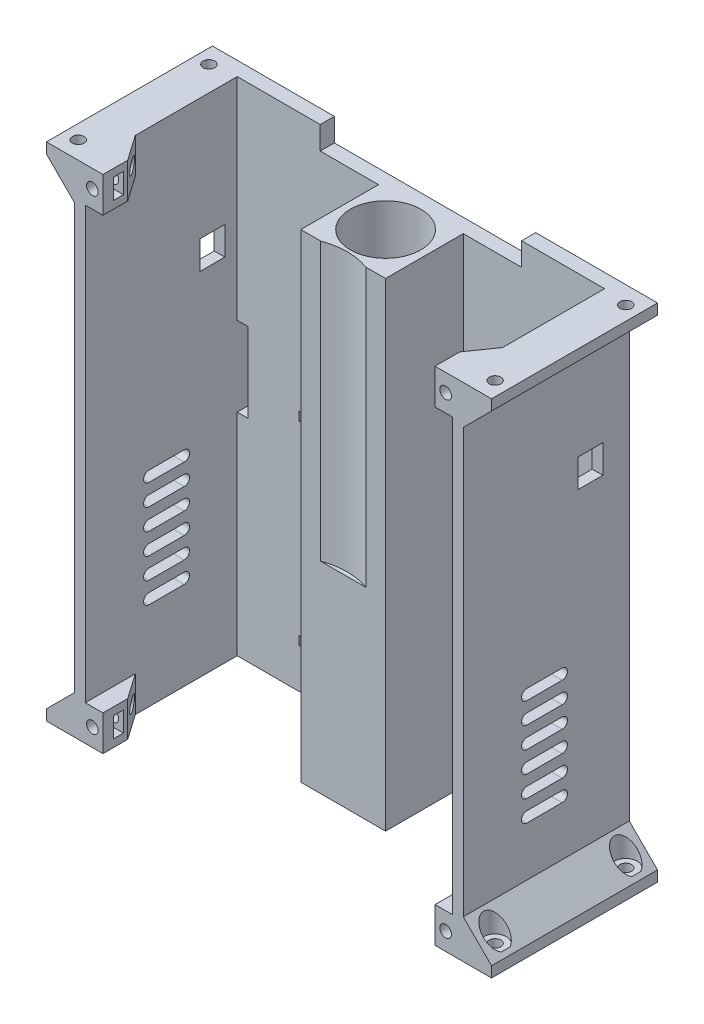
SolidWorks part; units mm, degrees
material "ABS"
ref_plane "Front Plane" through (0, 0, 0) normal (0, 0, 1) x (1, 0, 0)
ref_plane "Top Plane" through (0, 0, 0) normal (0, 1, 0) x (1, 0, 0)
ref_plane "Right Plane" through (0, 0, 0) normal (1, 0, 0) x (0, 0, -1)
sketch "Sketch1" plane through (0, 0, 0) normal (0, 0, 1) x (1, 0, 0)
  line L0 (-42, 71) -> (-42, 67)
  line L1 (-55, 71) -> (55, 71)
  line L2 (-55, 71) -> (-55, -71)
  line L3 (-55, -71) -> (55, -71)
  line L4 (55, 71) -> (55, -71)
  line L5 (-55, 71) -> (55, -71) construction
  line L6 (-55, -71) -> (55, 71) construction
  line L7 (-42, 67) -> (-52, 67)
  line L8 (-52, 71) -> (-52, -71)
  line L9 (-52, -67) -> (-42, -67)
  line L10 (-42, -67) -> (-42, -71)
  line L11 (42, -71) -> (42, -67)
  line L12 (42, -67) -> (52, -67)
  line L13 (52, -71) -> (52, 71)
  line L14 (52, 67) -> (42, 67)
  line L15 (42, 67) -> (42, 71)
  point P0 (0, 0)
  dimension "D2" = 142
  dimension "D3" = 10
  dimension "D4" = 10
  dimension "D5" = 3
  dimension "D6" = 3
  dimension "D7" = 4
  dimension "D8" = 4
  dimension "D9" = 4
  dimension "D10" = 4
  dimension "D11" = 10
  dimension "D12" = 10
  dimension "D13" = 104
extrude "Boss-Extrude1" add sketch "Sketch1" against normal blind 4 contours L14 L15 L1 L0 L7 L8 L9 L10 L3 L11 L12 L13 | L10 L9 L8 L7 L0 L1 L2 L3 | L15 L14 L13 L12 L11 L3 L4 L1 | L15 L14 L13 L1 | L1 L8 L7 L0 | L10 L9 L8 L3 | L3 L13 L12 L11 region at (0, 0, 0) region at (-47, 69, 0) region at (-53.5, 0, 0) region at (47, 69, 0) region at (53.5, 0, 0) region at (-47, -69, 0) region at (47, -69, 0)
extrude "Boss-Extrude2" add sketch "Sketch1<3>" along normal blind 43 contours L10 L9 L8 L7 L0 L1 L2 L3 | L15 L14 L13 L12 L11 L3 L4 L1 region at (-53.5, 0, 0) region at (53.5, 0, 0)
sketch "Sketch1<3>" plane through (0, 0, 0) normal (0, 0, 1) x (1, 0, 0) same geometry as "Sketch1"
sketch "Sketch2" plane through (0, 0, 0) normal (0, 0, 1) x (1, 0, 0)
  line L0 (-52, 71) -> (52, 71) construction
  line L1 (-10.5, -67) -> (-7.5, -67)
  line L2 (-10.5, -67) -> (-10.5, 71)
  line L3 (-10.5, 71) -> (-7.5, 71)
  line L4 (-7.5, -67) -> (-7.5, 71)
  line L5 (-10.5, -67) -> (-7.5, 71) construction
  line L6 (-10.5, 71) -> (-7.5, -67) construction
  line L8 (7.5, -67) -> (10.5, -67)
  line L9 (7.5, -67) -> (7.5, 71)
  line L10 (7.5, 71) -> (10.5, 71)
  line L11 (10.5, -67) -> (10.5, 71)
  line L12 (7.5, -67) -> (10.5, 71) construction
  line L13 (7.5, 71) -> (10.5, -67) construction
  point P0 (-9, 2)
  point P7 (9, 2)
  dimension "D1" = 3
  dimension "D2" = 3
  dimension "D3" = 7.5
  dimension "D4" = 15
extrude "Boss-Extrude3" [suppressed] add sketch "Sketch2" along normal blind 20
chamfer "Chamfer2" [suppressed] distance 0.5 angle 45
sketch "Sketch8" plane through (0, 0, 0) normal (0, 0, 1) x (1, 0, 0)
  line L0 (-52, -71) -> (52, -71) construction
  line L1 (10, -71) -> (12, -71)
  line L2 (10, -71) -> (10, 71)
  line L3 (10, 71) -> (12, 71)
  line L4 (12, -71) -> (12, 71)
  line L5 (-52, 71) -> (52, 71) construction
  line L7 (-10, -71) -> (-12, -71)
  line L8 (-10, -71) -> (-10, 71)
  line L9 (-10, 71) -> (-12, 71)
  line L10 (-12, -71) -> (-12, 71)
  dimension "D1" = 2
  dimension "D2" = 2
  dimension "D3" = 10
  dimension "D4" = 10
sketch "Sketch11" plane through (0, 0, 43) normal (0, 0, 1) x (1, 0, 0)
  line L0 (55, 71) -> (63, 71)
  line L1 (63, 71) -> (63, 68)
  line L2 (63, 68) -> (55, 60)
  line L3 (55, 71) -> (55, -71) construction
  line L4 (55, 60) -> (55, 71)
  dimension "D1" = 3
  dimension "D2" = 8
  dimension "D3" = 11
extrude "Boss-Extrude10" add sketch "Sketch11" against normal up to surface (47 mm away) up to face at (0, 0, -4)
sketch "Sketch12" plane through (0, 71, 0) normal (0, 1, 0) x (1, 0, 0)
  line L0 (63, 4) -> (63, -43) construction
  line L1 (52, -43) -> (63, -43) construction
  circle A0 centre (59, -38) radius 1.65
  circle A1 centre (59, -38) radius 3.25
  circle A2 centre (59, -1) radius 1.65
  circle A3 centre (59, -1) radius 3.25
  dimension "D1" = 3.3
  dimension "D2" = 6.5
  dimension "D5" = 3.3
  dimension "D6" = 6.5
  dimension "D3" = 4
  dimension "D4" = 5
  dimension "D7" = 37
extrude "Cut-Extrude3" cut sketch "Sketch12" against normal blind 14 contours A0 | A2 region at (59, 71, 38) region at (59, 71, 1)
extrude "Cut-Extrude4" cut sketch "Sketch12<3>" against normal blind 14 from offset 4 offset against normal yes
sketch "Sketch12<3>" plane through (0, 71, 0) normal (0, 1, 0) x (1, 0, 0) same geometry as "Sketch12"
sketch "Sketch13" plane through (0, 71, 0) normal (0, 1, 0) x (1, 0, 0)
  line L0 (52, -43) -> (47, -43)
  line L1 (47, -43) -> (47, -36)
  line L2 (47, -36) -> (52, -28.8593)
  line L3 (52, -43) -> (52, 0) construction
  line L4 (52, -28.8593) -> (52, -43)
  dimension "D1" = 5
  dimension "D2" = 7
  dimension "D3" = 35
extrude "Boss-Extrude11" add sketch "Sketch13" against normal blind 10
sketch "Sketch14" plane through (0, 0, 43) normal (0, 0, 1) x (1, 0, 0)
  line L0 (47, 61) -> (47, 71) construction
  line L1 (47, 71) -> (63, 71) construction
  line L3 (47, 68.85) -> (53.5, 68.85)
  line L4 (47, 68.85) -> (47, 63.15)
  line L5 (47, 63.15) -> (53.5, 63.15)
  line L6 (53.5, 68.85) -> (53.5, 63.15)
  circle A0 centre (50, 66) radius 1.65
  point P11 (53.5, 66)
  dimension "D3" = 3.3
  dimension "D1" = 3
  dimension "D2" = 5
  dimension "D4" = 5.7
  dimension "D5" = 6.5
extrude "Cut-Extrude5" cut sketch "Sketch14" against normal blind 18 contours A0 region at (50, 66, 43)
extrude "Cut-Extrude6" cut sketch "Sketch14<3>" against normal blind 2.8 from offset 3 offset against normal yes
sketch "Sketch14<3>" plane through (0, 0, 43) normal (0, 0, 1) x (1, 0, 0) same geometry as "Sketch14"
mirror "Mirror1" about plane through (0, 0, 0) normal (0, 1, 0) of "Cut-Extrude6", "Cut-Extrude5", "Boss-Extrude11", "Boss-Extrude10", "Cut-Extrude3", "Cut-Extrude4"
mirror "Mirror2" about plane through (0, 0, 0) normal (1, 0, 0) of "Cut-Extrude6", "Cut-Extrude5", "Boss-Extrude11", "Boss-Extrude10", "Cut-Extrude3", "Cut-Extrude4", "Mirror1"
sketch "Sketch17" plane through (0, -71, 0) normal (0, -1, 0) x (1, 0, 0)
  line L1 (-52, 0) -> (52, 0) construction
  line L2 (-9.99, 10) -> (-9.99, 0)
  line L3 (-9.99, 0) -> (-12, 0)
  line L4 (-12, 0) -> (-12, 10)
  line L5 (9.99, 10) -> (9.99, 0)
  line L6 (9.99, 0) -> (12, 0)
  line L7 (12, 0) -> (12, 10)
  line L8 (-9.99, 0) -> (9.99, 0)
  line L9 (12, 10) -> (9.99, 10)
  line L10 (0, 0.01) -> (0, 0)
  line L11 (-12, 10) -> (-12, 22)
  line L12 (-12, 22) -> (12, 22)
  line L13 (12, 22) -> (12, 10)
  circle A0 centre (0, 10) radius 9.99
  arc A1 (-12, 10) -> (12, 10) centre (0, 10) cw
  point P8 (0, 0)
  line M5 (52, 0) -> (-52, 0)
  dimension "D1" = 19.98
  dimension "D2" = 12
  dimension "D3" = 10
extrude "Boss-Extrude12" add sketch "Sketch17" against normal up to surface (142 mm away) contours A1 L4 L2 A0 L5 L7 M5 | A0 L2 L8 | A0 L5 L7 L9 M5 | L11 A1 L12 | L12 A1 L13 | A0 L10 L5 M5 region at (-7.7457, -71, 2.2311) region at (-10.3156, -71, 5) region at (10.995, -71, 5) region at (7.7457, -71, 2.2311) region at (9.3196, -71, 19.3196) region at (-9.3196, -71, 19.3196) up to face at (-59, 71, 39.65)
sketch "Sketch18" plane through (0, 0, 0) normal (0, 0, 1) x (1, 0, 0)
  line L0 (-52, -71) -> (-12, -71) construction
  line L1 (-34.5, -57.25) -> (-29.5, -57.25)
  line L2 (-34.5, -57.25) -> (-34.5, -59.75)
  line L3 (-34.5, -59.75) -> (-29.5, -59.75)
  line L4 (-29.5, -57.25) -> (-29.5, -59.75)
  line L5 (-34.5, -57.25) -> (-29.5, -59.75) construction
  line L6 (-34.5, -59.75) -> (-29.5, -57.25) construction
  line L7 (-34.5, -2.25) -> (-29.5, -2.25)
  line L8 (-34.5, -2.25) -> (-34.5, -4.75)
  line L9 (-34.5, -4.75) -> (-29.5, -4.75)
  line L10 (-29.5, -2.25) -> (-29.5, -4.75)
  line L11 (-34.5, -2.25) -> (-29.5, -4.75) construction
  line L12 (-34.5, -4.75) -> (-29.5, -2.25) construction
  line L13 (52, -71) -> (52, 71) construction
  line L14 (12, -11.25) -> (15, -11.25)
  line L15 (12, -11.25) -> (12, 11.25)
  line L16 (12, 11.25) -> (15, 11.25)
  line L17 (15, -11.25) -> (15, 11.25)
  line L18 (12, -11.25) -> (15, 11.25) construction
  line L19 (12, 11.25) -> (15, -11.25) construction
  line L20 (49, -11.25) -> (52, -11.25)
  line L21 (49, -11.25) -> (49, 11.25)
  line L22 (49, 11.25) -> (52, 11.25)
  line L23 (52, -11.25) -> (52, 11.25)
  line L24 (49, -11.25) -> (52, 11.25) construction
  line L25 (49, 11.25) -> (52, -11.25) construction
  line L26 (12, -71) -> (12, 71) construction
  point P0 (-32, -58.5)
  point P5 (-32, -3.5)
  point P10 (50.5, 0)
  point P14 (13.5, 0)
  point P31 (-32, -71)
  dimension "D1" = 12.5
  dimension "D2" = 52.5
  dimension "D3" = 2.5
  dimension "D4" = 5
  dimension "D5" = 22.5
  dimension "D6" = 3
extrude "Cut-Extrude7" cut sketch "Sketch18" against normal blind 15.1
sketch "Sketch19" plane through (0, 71, 0) normal (0, 1, 0) x (1, 0, 0)
  line L1 (-52, 0) -> (-12, 0) construction
  line L2 (-63, 4) -> (63, 4) construction
  circle A0 centre (0, -39.35) radius 18.5
  point P7 (0, 4)
  dimension "D2" = 37
  dimension "D1" = 39.35
extrude "Cut-Extrude8" cut sketch "Sketch19" against normal blind 85
sketch "Sketch20" plane through (0, 0, -4) normal (0, 0, -1) x (-1, 0, 0)
  line L0 (63, 71) -> (-63, 71) construction
  line L1 (-28.5, 64.5) -> (28.5, 64.5)
  line L2 (-28.5, 64.5) -> (-28.5, 71)
  line L3 (-28.5, 71) -> (28.5, 71)
  line L4 (28.5, 64.5) -> (28.5, 71)
  line L5 (-28.5, 64.5) -> (28.5, 71) construction
  line L6 (-28.5, 71) -> (28.5, 64.5) construction
  point P0 (0, 67.75)
  dimension "D1" = 57
  dimension "D2" = 6.5
extrude "Cut-Extrude9" cut sketch "Sketch20" against normal blind 47
mirror "Mirror3" about plane through (0, 0, 0) normal (1, 0, 0) of "Cut-Extrude7"
sketch "Sketch21" plane through (-55, 0, 0) normal (-1, 0, 0) x (0, 0, 1)
  line L0 (25, -44.5) -> (15, -44.5) construction
  line L1 (25, -46) -> (15, -46)
  line L2 (25, -43) -> (15, -43)
  line L3 (-4, 60) -> (-4, -60) construction
  line L4 (-4, -71) -> (43, -71) construction
  line L5 (25, -38.5) -> (15, -38.5) construction
  line L6 (25, -40) -> (15, -40)
  line L7 (25, -37) -> (15, -37)
  line L8 (25, -32.5) -> (15, -32.5) construction
  line L9 (25, -34) -> (15, -34)
  line L10 (25, -31) -> (15, -31)
  line L11 (25, -26.5) -> (15, -26.5) construction
  line L12 (25, -28) -> (15, -28)
  line L13 (25, -25) -> (15, -25)
  line L14 (25, -20.5) -> (15, -20.5) construction
  line L15 (25, -22) -> (15, -22)
  line L16 (25, -19) -> (15, -19)
  line L17 (25, -14.5) -> (15, -14.5) construction
  line L18 (25, -16) -> (15, -16)
  line L19 (25, -13) -> (15, -13)
  arc A0 (25, -46) -> (25, -43) centre (25, -44.5) ccw
  arc A1 (15, -43) -> (15, -46) centre (15, -44.5) ccw
  arc A2 (25, -40) -> (25, -37) centre (25, -38.5) ccw
  arc A3 (15, -37) -> (15, -40) centre (15, -38.5) ccw
  arc A4 (25, -34) -> (25, -31) centre (25, -32.5) ccw
  arc A5 (15, -31) -> (15, -34) centre (15, -32.5) ccw
  arc A6 (25, -28) -> (25, -25) centre (25, -26.5) ccw
  arc A7 (15, -25) -> (15, -28) centre (15, -26.5) ccw
  arc A8 (25, -22) -> (25, -19) centre (25, -20.5) ccw
  arc A9 (15, -19) -> (15, -22) centre (15, -20.5) ccw
  arc A10 (25, -16) -> (25, -13) centre (25, -14.5) ccw
  arc A11 (15, -13) -> (15, -16) centre (15, -14.5) ccw
  point P2 (20, -44.5)
  point P15 (20, -38.5)
  point P22 (20, -32.5)
  point P29 (20, -26.5)
  point P36 (20, -20.5)
  point P41 (20, -14.5)
  dimension "D1" = 10
  dimension "D2" = 3
  dimension "D3" = 19
  dimension "D4" = 25
  dimension "D5" = 6
extrude "Cut-Extrude10" cut sketch "Sketch21" against normal blind 10
mirror "Mirror4" about plane through (0, 0, 0) normal (1, 0, 0) of "Cut-Extrude10"
sketch "Sketch22" plane through (55, 0, 0) normal (1, 0, 0) x (0, 0, -1)
  line L1 (4, 60) -> (-43, 60) construction
  line L2 (-16.5, -13) -> (-16.5, 60) construction
  line L3 (4, 60) -> (4, -60) construction
  text T1 "<b>STORM</b>" font "Sofachrome Rg" height 7
  dimension "D1" = 20.5
extrude "Boss-Extrude13" [suppressed] add sketch "Sketch22" along normal blind 0.5
sketch "Sketch23" plane through (-55, 0, 0) normal (-1, 0, 0) x (0, 0, 1)
  line L0 (16.5, -13) -> (16.5, 60) construction
  line L5 (-4, 60) -> (43, 60) construction
  line L7 (-4, 60) -> (-4, -60) construction
  text T1 "<b>STORM</b>" font "Sofachrome Rg" height 7
  dimension "D2" = 20.5
extrude "Boss-Extrude14" [suppressed] add sketch "Sketch23" along normal blind 0.5
sketch "Sketch24" plane through (-52, 0, 0) normal (1, 0, 0) x (0, 0, -1)
  line L0 (0, 71) -> (0, 11.25) construction
  line L1 (-14, 19) -> (0, 19) construction
  line L2 (-14, 19) -> (-14, 46) construction
  line L3 (-14, 46) -> (0, 46) construction
  line L4 (0, 19) -> (0, 46) construction
  line L5 (-28.8593, 71) -> (0, 71) construction
  line L6 (0, 46) -> (-14, 19) construction
  line L7 (-14, 46) -> (0, 19) construction
  line L9 (-3.5, 36.5) -> (-10.5, 36.5)
  line L10 (-3.5, 36.5) -> (-3.5, 28.5)
  line L11 (-3.5, 28.5) -> (-10.5, 28.5)
  line L12 (-10.5, 36.5) -> (-10.5, 28.5)
  line L13 (-3.5, 36.5) -> (-10.5, 28.5) construction
  line L14 (-3.5, 28.5) -> (-10.5, 36.5) construction
  point P9 (-7, 32.5)
  point P15 (-7, 32.5)
  dimension "D1" = 14
  dimension "D2" = 27
  dimension "D3" = 25
  dimension "D4" = 7.75
  dimension "D5" = 7
  dimension "D6" = 8
  dimension "D7" = 7
extrude "Cut-Extrude12" cut sketch "Sketch24" against normal blind 15
mirror "Mirror5" about plane through (0, 0, 0) normal (1, 0, 0) of "Cut-Extrude12"
equation "\"D8@Sketch1\"=\"D7@Sketch1\""
equation "\"D4@Sketch1\"=\"D3@Sketch1\""
equation "\"D5@Sketch1\"=\"D6@Sketch1\""
equation "\"D9@Sketch1\"=\"D7@Sketch1\""
equation "\"D10@Sketch1\"=\"D7@Sketch1\""
equation "\"D11@Sketch1\"=\"D3@Sketch1\""
equation "\"D12@Sketch1\"=\"D3@Sketch1\""
equation "\"D3@Sketch2\"=\"D4@Sketch2\"/2"
equation "\"D2@Sketch2\"=\"D1@Sketch2\""
